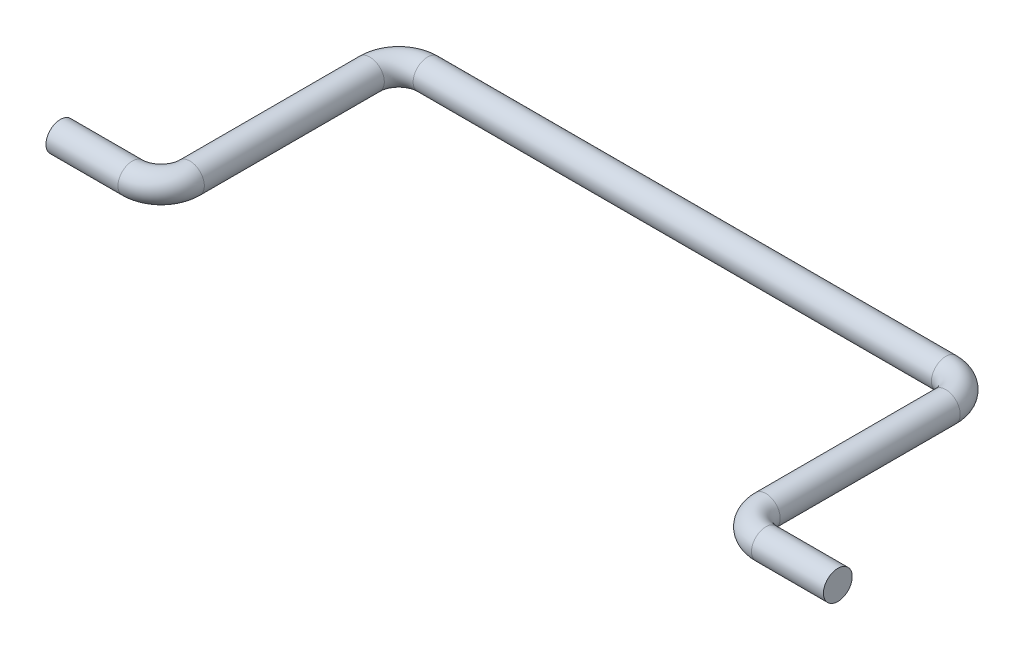
SolidWorks part; units mm, degrees
ref_plane "Front Plane" through (0, 0, 0) normal (0, 0, 1) x (1, 0, 0)
ref_plane "Top Plane" through (0, 0, 0) normal (0, 1, 0) x (1, 0, 0)
ref_plane "Right Plane" through (0, 0, 0) normal (1, 0, 0) x (0, 0, -1)
sketch "Sketch1" plane through (0, 0, 0) normal (0, 1, 0) x (1, 0, 0)
  line L0 (0, -150.3728) -> (0, 7368.2684) construction
  line L1 (-150.3728, 0) -> (7368.2684, 0) construction
  line L2 (-160.4113, 8.25) -> (7358.23, 8.25) construction
  line L3 (-13.5, -147.7382) -> (-13.5, 7370.9031) construction
  line L4 (13.5, -147.7382) -> (13.5, 7370.9031) construction
  line L5 (-10, -996.1346) -> (-10, 49003.8654) construction
  line L6 (10, -996.1346) -> (10, 49003.8654) construction
  line L7 (-13.5, 0) -> (-11, 0)
  line L8 (-10, 1) -> (-10, 7.25)
  line L9 (-9, 8.25) -> (9, 8.25)
  line L10 (10, 7.25) -> (10, 1)
  line L11 (11, 0) -> (13.5, 0)
  arc A0 (-10, 7.25) -> (-9, 8.25) centre (-9, 7.25) cw
  arc A1 (9, 8.25) -> (10, 7.25) centre (9, 7.25) cw
  arc A2 (10, 1) -> (11, 0) centre (11, 1) ccw
  arc A3 (-11, 0) -> (-10, 1) centre (-11, 1) ccw
  point P23 (-10, 8.25)
  point P26 (10, 8.25)
  point P29 (10, 0)
  point P32 (-10, 0)
  point P33 (0, 0)
  point P34 (0, 0)
  point P35 (0, 0)
  dimension "D4" = 1
  dimension "D1" = 8.25
  dimension "D2" = 13.5
  dimension "D3" = 10
ref_plane "Plane1" through (-13.5, 0, 0) normal (1, 0, 0) x (0, 0, -1)
sketch "Sketch4" plane through (-13.5, 0, 0) normal (1, 0, 0) x (0, 0, -1)
  circle A0 centre (0, 0) radius 0.5
sweep "Sweep1" add profiles "Sketch4" path "Sketch1"
